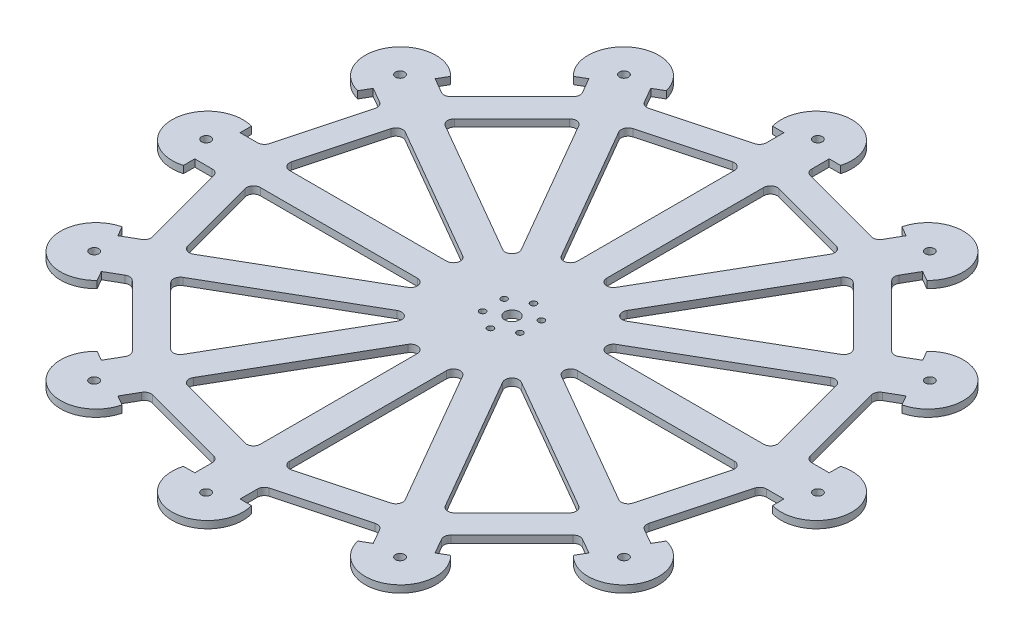
SolidWorks part; units mm, degrees
ref_plane "Front Plane" through (0, 0, 0) normal (0, 0, 1) x (1, 0, 0)
ref_plane "Top Plane" through (0, 0, 0) normal (0, 1, 0) x (1, 0, 0)
ref_plane "Right Plane" through (0, 0, 0) normal (1, 0, 0) x (0, 0, -1)
sketch "Sketch1" plane through (0, 0, 0) normal (0, 1, 0) x (1, 0, 0)
  line L0 (0, 0) -> (0, 150)
  line L1 (15, 130) -> (10, 130)
  line L2 (10, 130) -> (10, 120)
  line L3 (10, 120) -> (30.6699, 114.4615)
  line L4 (0, 0) -> (36.1011, 134.7312) construction
  line L5 (30.6699, 114.4615) -> (27.564, 102.8704)
  line L6 (27.564, 102.8704) -> (6.4705, 108.5224)
  line L7 (6.4705, 108.5224) -> (6.4705, 24.1481)
  line L8 (6.4705, 24.1481) -> (0, 0)
  arc A1 (0, 150) -> (15, 130) centre (0, 134.375) cw
  dimension "D3" = 5
  dimension "D1" = 15
  dimension "D2" = 15
  dimension "D4" = 10
  dimension "D5" = 20
  dimension "D6" = 150
  dimension "D7" = 25
  dimension "D8" = 12
extrude "Boss-Extrude1" add sketch "Sketch1" along normal blind 3.18
mirror "Mirror1" about plane through (30.6699, 3.18, -114.4615) normal (-0.9659, 0, -0.2588) of "Boss-Extrude1"
fillet "Fillet1" radius 3 5 edges at (6.4705, 1.59, -24.1481) (48.6576, 1.59, -97.2184) (6.4705, 1.59, -108.5224) (51.3397, 1.59, -108.923) (10, 1.59, -120)
ref_axis "Axis1" through (0, 3.18, 0) along (0, -1, 0)
pattern_circular "CirPattern27" count 12 over 360 about axis through (0, 3.18, 0) along (0, -1, 0) of bodies 102
combine bodies "Combine1" bodies to combine 110 111 112 113 102 103 104 105 106 107 108 109
sketch "Sketch3" plane through (0, 3.18, 0) normal (0, 1, 0) x (1, 0, 0)
  circle A0 centre (0, 0) radius 3.175
  dimension "D1" = 6.35
extrude "Cut-Extrude1" cut sketch "Sketch3" against normal through all
sketch "Sketch4" plane through (0, 3.18, 0) normal (0, 1, 0) x (1, 0, 0)
  line L0 (0, 0) -> (0, 15.97) construction
  circle A0 centre (0, 9.5) radius 1.35
  circle A1 centre (8.2272, 4.75) radius 1.35
  circle A2 centre (8.2272, -4.75) radius 1.35
  circle A3 centre (0, -9.5) radius 1.35
  circle A4 centre (-8.2272, -4.75) radius 1.35
  circle A5 centre (-8.2272, 4.75) radius 1.35
  point P19 (0, 0)
  dimension "D1" = 2.7
  dimension "9.5" = 9.5
  dimension "D2" = 6
extrude "Cut-Extrude2" cut sketch "Sketch4" against normal through all
sketch "Sketch5" plane through (0, 3.18, 0) normal (0, 1, 0) x (1, 0, 0)
  line L0 (0, 0) -> (0, 115.9813) construction
  circle A0 centre (0, 135) radius 2
  dimension "D1" = 4
  dimension "D2" = 135
extrude "Cut-Extrude3" cut sketch "Sketch5" against normal through all
pattern_circular "CirPattern28" count 12 every 30 about axis through (0, 3.18, 0) along (0, -1, 0) of "Cut-Extrude3"
